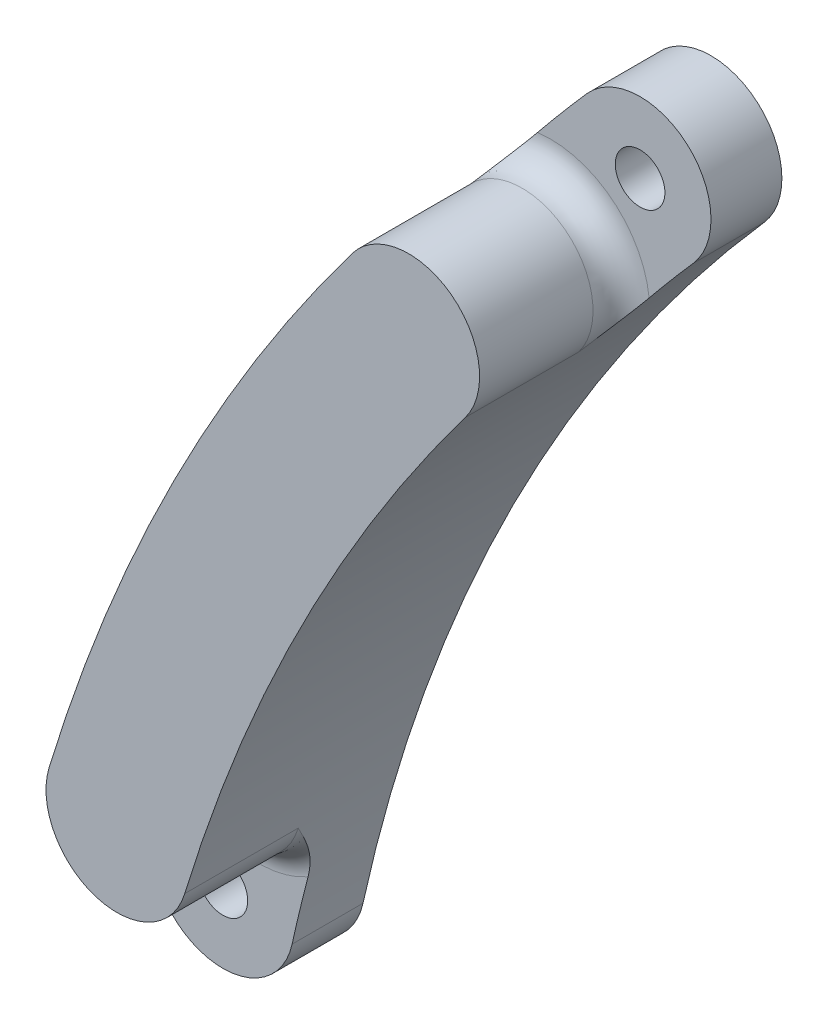
SolidWorks part; units mm, degrees
ref_plane "Plan de face" through (0, 0, 0) normal (0, 0, 1) x (1, 0, 0)
ref_plane "Plan de dessus" through (0, 0, 0) normal (0, 1, 0) x (1, 0, 0)
ref_plane "Plan de droite" through (0, 0, 0) normal (1, 0, 0) x (0, 0, -1)
sketch "Esquisse1" plane through (0, 0, 0) normal (0, 0, 1) x (1, 0, 0)
  arc A0 (0, 0) -> (29.4235, 57.9591) centre (126.9491, -27.9989) cw construction
  arc A1 (25.6726, 61.2652) -> (-4.8827, 1.0769) centre (126.9491, -27.9989) ccw
  arc A2 (33.1745, 54.653) -> (4.8827, -1.0769) centre (126.9491, -27.9989) ccw
  arc A3 (33.1745, 54.653) -> (25.6726, 61.2652) centre (29.4235, 57.9591) ccw
  arc A4 (-4.8827, 1.0769) -> (4.8827, -1.0769) centre (0, 0) ccw
  circle A5 centre (0, 0) radius 1.75
  circle A6 centre (29.4235, 57.9591) radius 1.75
  point P3 (11.0309, 30.8482)
  dimension "D2" = 130
  dimension "D3" = 3.5
  dimension "D1" = 65
  dimension "D4" = 10
extrude "Boss.-Extru.1" add sketch "Esquisse1" along normal blind 5
sketch "Esquisse2" plane through (0, 0, 5) normal (0, 0, 1) x (1, 0, 0)
  arc A0 (0, 0) -> (29.4235, 57.9591) centre (126.9491, -27.9989) cw construction
  arc A1 (2.5278, 9.6752) -> (23.1048, 50.2084) centre (126.9491, -27.9989) cw construction
  arc A2 (19.1108, 53.2163) -> (-2.2577, 11.1243) centre (126.9491, -27.9989) ccw
  arc A3 (27.0988, 47.2004) -> (7.3132, 8.2262) centre (126.9491, -27.9989) ccw
  arc A4 (27.0988, 47.2004) -> (19.1108, 53.2163) centre (23.1048, 50.2084) ccw
  arc A5 (-2.2577, 11.1243) -> (7.3132, 8.2262) centre (2.5278, 9.6752) ccw
  point P8 (11.0309, 30.8482)
  dimension "D4" = 10
  dimension "D1" = 130
  dimension "D2" = 10
  dimension "D3" = 10
extrude "Boss.-Extru.2" add sketch "Esquisse2" along normal blind 10
fillet "Congé1" radius 2 2 edges at (26.1128, 54.2024, 5) (1.0788, 4.8898, 5)
